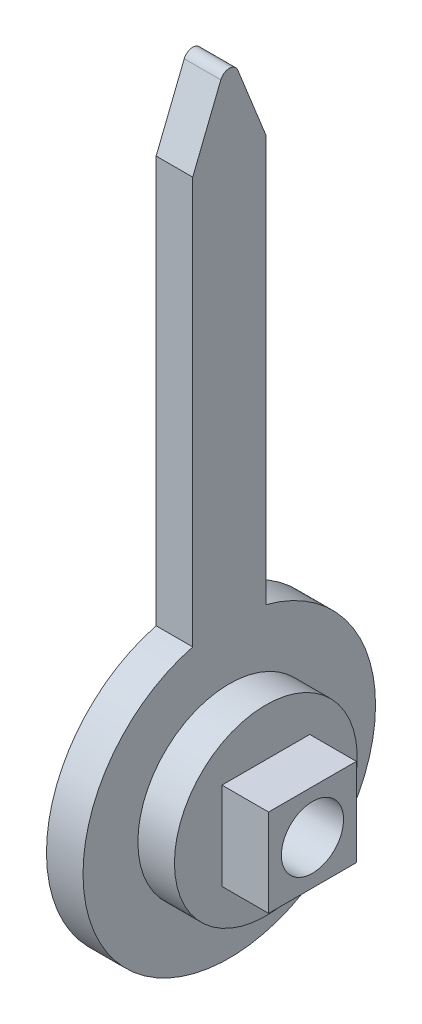
SolidWorks part; units mm, degrees
ref_plane "Front" through (0, 0, 0) normal (0, 0, 1) x (1, 0, 0)
ref_plane "Top" through (0, 0, 0) normal (0, 1, 0) x (1, 0, 0)
ref_plane "Right" through (0, 0, 0) normal (1, 0, 0) x (0, 0, -1)
sketch "Sketch1" plane through (-2, 0, 0) normal (-1, 0, 0) x (0, 0, 1)
  line L0 (0, 30) -> (0, 0) construction
  line L2 (-2, 30) -> (-2, 0)
  line L3 (-2, 0) -> (2, 0)
  line L4 (2, 30) -> (2, 0)
  line L5 (-2, 30) -> (-0.4642, 33.8394)
  line L6 (0, -200060) -> (0, 237734.0135) construction
  line L7 (0.4642, 33.8394) -> (2, 30)
  line L8 (-2, 30) -> (2, 30) construction
  line L14 (2.4, -2.4) -> (2.4, 2.4)
  line L15 (2.4, -2.4) -> (2.4, 2.4)
  line L16 (-2.4, -2.4) -> (2.4, -2.4)
  line L17 (-2.4, -2.4) -> (2.4, -2.4)
  line L18 (-2.4, 2.4) -> (-2.4, -2.4)
  line L19 (-2.4, 2.4) -> (-2.4, -2.4)
  line L20 (2.4, 2.4) -> (-2.4, 2.4)
  line L21 (2.4, 2.4) -> (-2.4, 2.4)
  arc A0 (-0.4642, 33.8394) -> (0.4642, 33.8394) centre (0, 33.6537) cw
  circle A1 centre (0, 0) radius 8
  circle A2 centre (0, 0) radius 5
  point P14 (0, 35)
  dimension "D4" = 0.5
  dimension "D5" = 16
  dimension "D7" = 10
  dimension "D1" = 4
  dimension "D2" = 30
  dimension "D3" = 5
  dimension "D6" = 0.1
extrude "Boss-Extrude1" add sketch "Sketch1" against normal up to surface (2.55 mm away) contours L4 L3 L2 | L4 L2 L3 region at (-2, 1.2, 0) region at (-2, -0.8571, 0)
extrude "Boss-Extrude2" add sketch "Sketch1<4>" along normal blind 2 contours A2
sketch "Sketch1<4>" plane through (-2, 0, 0) normal (-1, 0, 0) x (0, 0, 1) same geometry as "Sketch1"
extrude "Boss-Extrude3" add sketch "Sketch1<5>" along normal blind 2 from surface contours A1 | L4 L3 L2 L5 A0 L7 starting at face at (-4, 0, 5)
sketch "Sketch1<5>" plane through (-2, 0, 0) normal (-1, 0, 0) x (0, 0, 1) same geometry as "Sketch1"
sketch "Sketch2" plane through (-6, 0, 0) normal (-1, 0, 0) x (0, 0, 1)
  circle A0 centre (0, 0) radius 2.85
  circle A1 centre (0, 0) radius 1.7
  dimension "D1" = 5.7
  dimension "D2" = 3.4
extrude "Cut-Extrude1" cut sketch "Sketch2" against normal blind 2.5 contours A0
extrude "Cut-Extrude2" cut sketch "Sketch2<3>" against normal through all contours A1 region at (-6, 0, 0)
sketch "Sketch2<3>" plane through (-6, 0, 0) normal (-1, 0, 0) x (0, 0, 1) same geometry as "Sketch2"
